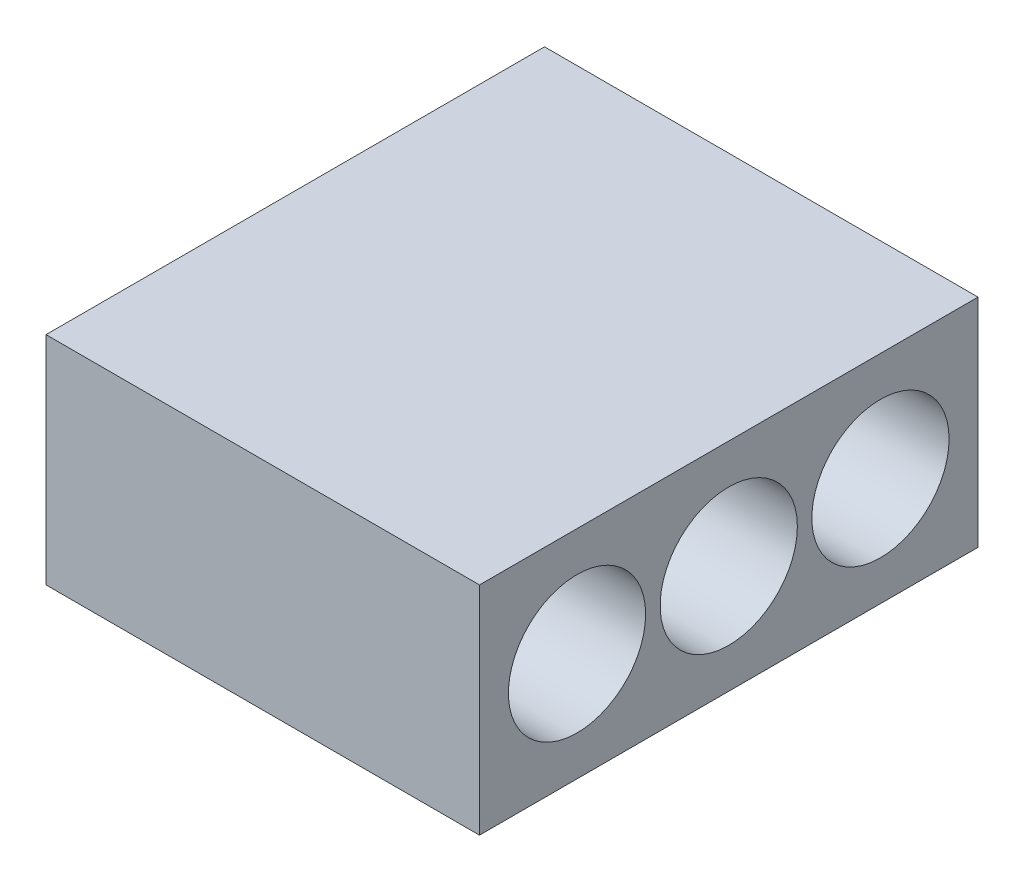
SolidWorks part; units mm, degrees
ref_plane "Front Plane" through (0, 0, 0) normal (0, 0, 1) x (1, 0, 0)
ref_plane "Top Plane" through (0, 0, 0) normal (0, 1, 0) x (1, 0, 0)
ref_plane "Right Plane" through (0, 0, 0) normal (1, 0, 0) x (0, 0, -1)
sketch "Sketch1" plane through (0, 0, 0) normal (0, 1, 0) x (1, 0, 0)
  line L1 (0, 0) -> (100, 0)
  line L2 (0, 0) -> (0, 115)
  line L3 (0, 115) -> (100, 115)
  line L4 (100, 0) -> (100, 115)
  dimension "D1" = 115
  dimension "D2" = 100
extrude "Boss-Extrude1" add sketch "Sketch1" along normal blind 50
sketch "Sketch3" plane through (100, 0, 0) normal (1, 0, 0) x (0, 0, -1)
  line L0 (57.5, 50) -> (57.5, 0) construction
  line L1 (0, 50) -> (115, 50) construction
  line L2 (0, 0) -> (115, 0) construction
  line L3 (57.5, 25) -> (92.5, 25) construction
  line L4 (57.5, 25) -> (22.5, 25) construction
  circle A0 centre (57.5, 25) radius 15.83
  circle A1 centre (92.5, 25) radius 15.83
  circle A2 centre (22.5, 25) radius 15.83
  dimension "D1" = 31.66
  dimension "D6" = 25
  dimension "D3" = 35
  dimension "D5" = 35
  dimension "D7" = 25
  dimension "D2" = 2
  dimension "D4" = 2
extrude "Cut-Extrude2" cut sketch "Sketch3" against normal up to next
